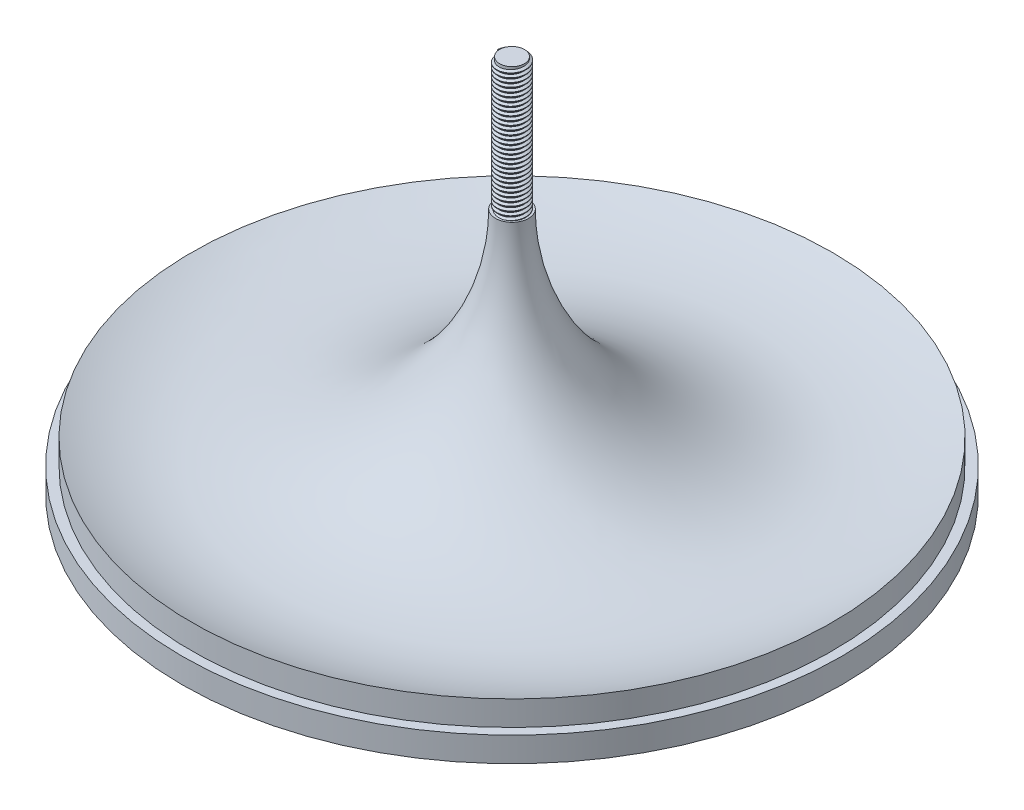
SolidWorks part; units mm, degrees
material "Polybutadiene (PB)"
ref_plane "Front Plane" through (0, 0, 0) normal (0, 0, 1) x (1, 0, 0)
ref_plane "Top Plane" through (0, 0, 0) normal (0, 1, 0) x (1, 0, 0)
ref_plane "Right Plane" through (0, 0, 0) normal (1, 0, 0) x (0, 0, -1)
sketch "Sketch2" plane through (0, 0, 0) normal (0, 0, 1) x (1, 0, 0)
  line L0 (0, 0) -> (15, 0)
  line L1 (15, 0) -> (20, 0)
  line L5 (0, 0) -> (0, 15)
  line L6 (19.4307, 1.5) -> (19.4307, 3)
  line L7 (19.4307, 1.5) -> (20, 1.5)
  line L8 (20, 1.5) -> (20, 0)
  line L9 (0, 15) -> (1, 15)
  arc A1 (1, 15) -> (19.4307, 3) centre (14.1219, 15) ccw
  dimension "D1" = 15
  dimension "D2" = 5
  dimension "D3" = 1.5
  dimension "D4" = 1.5
  dimension "D5" = 15
  dimension "D6" = 1
revolve "Revolve1" add sketch "Sketch2" angle 360 about L5
sketch "Sketch3" plane through (0, 15, 0) normal (0, 1, 0) x (1, 0, 0)
  circle A0 centre (0, 0) radius 0.75
  dimension "D1" = 1.5
extrude "Boss-Extrude1" add sketch "Sketch3" along normal blind 8
thread "Thread1" pitch 0.25 method extrude profile "Thread Profile1" start angle 0, offset 0, length 8, pitch 0.25, diameter 1.5
ref_plane "Plane1" through (-0.75, 23, 0) normal (0, 0, 1) x (-1, 0, 0)
sketch "Thread Profile1" plane through (-0.75, 23, 0) normal (0, 0, 1) x (-1, 0, 0)
  line L0 (0, 0) -> (0, 0.25) construction
  line L1 (0, 0) -> (0.1353, 0.0781)
  line L2 (0.1353, 0.0781) -> (0.1353, 0.1094)
  line L3 (0.1353, 0.1094) -> (0, 0.1875)
  line L4 (0.1353, 0.0937) -> (0, 0.0937) construction
  line L11 (0, 0) -> (0, 0.1875)
  point P2 (0, 0)
  dimension "Pitch" = 0.25
  dimension "Profile_Angle" = 60
  dimension "Profile_Land" = 0.0312
  dimension "Profile_Height" = 0.1353
